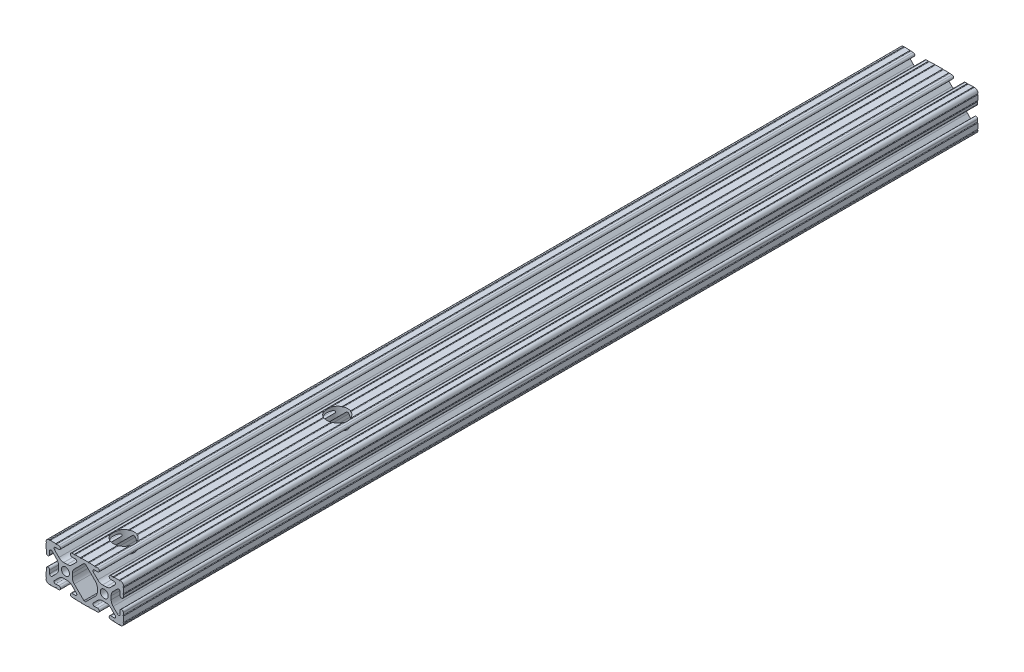
SolidWorks part; units mm, degrees
ref_plane "Front Plane" through (0, 0, 0) normal (0, 0, 1) x (1, 0, 0)
ref_plane "Top Plane" through (0, 0, 0) normal (0, 1, 0) x (1, 0, 0)
ref_plane "Right Plane" through (0, 0, 0) normal (1, 0, 0) x (0, 0, -1)
sketch "Sketch1" plane through (0, 0, 0) normal (0, 0, 1) x (1, 0, 0)
  line L0 (0, 12.7) -> (-12.7814, 12.7) construction
  line L1 (-4.5085, 0) -> (-4.5085, 2.9459)
  line L2 (-6.0437, 12.5461) -> (-10.0976, 12.6876) construction
  line L3 (-11.5616, 12.4229) -> (-4.3159, 12.1699) construction
  line L4 (-6.4364, 10.3486) -> (-6.3592, 12.5571) construction
  line L6 (-2.9459, 4.5085) -> (0, 4.5085)
  line L7 (0, 0) -> (0, 12.7) construction
  line L8 (0, 0) -> (-12.7814, 0) construction
  line L9 (0.7813, 0.7813) -> (-0.7813, -0.7813) construction
  line L10 (-2.9459, 4.5085) -> (-7.1484, 8.711)
  line L11 (-4.5085, 2.9459) -> (-8.711, 7.1484)
  line L13 (0, 0) -> (-12.7814, 12.7814) construction
  line L14 (-10.4131, 12.6987) -> (-4.3048, 12.4853)
  line L15 (-4.3048, 12.4853) -> (-4.382, 10.2769) construction
  line L16 (-4.382, 10.2769) -> (-6.4364, 10.3486)
  line L17 (-12.6987, 10.4131) -> (-12.4853, 4.3048)
  line L18 (-10.2769, 4.382) -> (-10.3486, 6.4364)
  circle A0 centre (0, 0) radius 2.6035
  arc A1 (-4.382, 10.2769) -> (-4.3048, 12.4853) centre (-4.3434, 11.3811) ccw
  arc A2 (-7.1484, 8.711) -> (-6.4364, 10.3486) centre (-6.4698, 9.3896) cw
  arc A3 (-8.711, 7.1484) -> (-10.3486, 6.4364) centre (-9.3896, 6.4698) ccw
  arc A4 (-10.2769, 4.382) -> (-12.4853, 4.3048) centre (-11.3811, 4.3434) cw
  arc A5 (-10.4131, 12.6987) -> (-12.6987, 10.4131) centre (-10.4902, 10.4902) ccw
  arc A6 (-10.4131, 12.6987) -> (-9.7821, 12.6766) centre (-10.0976, 12.6876) ccw
  arc A7 (-6.3592, 12.5571) -> (-5.7282, 12.5351) centre (-6.0437, 12.5461) ccw
  arc A8 (-12.5571, 6.3592) -> (-12.5351, 5.7282) centre (-12.5461, 6.0437) cw
  arc A9 (-12.6987, 10.4131) -> (-12.6766, 9.7821) centre (-12.6876, 10.0976) cw
  dimension "D1" = 5.207
  dimension "D5" = 14.859
  dimension "D9" = 2
  dimension "D2" = 25.4
  dimension "D12" = 0.6314
  dimension "D10" = 2.2098
  dimension "D3" = 9.017
  dimension "D4" = 9.017
  dimension "D6" = 25.4
  dimension "D7" = 6.477
  dimension "D8" = 2.2098
  dimension "D11" = 12.7
sketch "Sketch3" plane through (0, 0, 0) normal (0, 0, 1) x (1, 0, 0)
  line L0 (-2.9459, 4.5085) -> (0, 4.5085) construction
  line L1 (-2.9459, 4.5085) -> (-7.1484, 8.711) construction
  line L2 (-4.382, 10.2769) -> (-6.4364, 10.3486) construction
  line L3 (-10.4131, 12.6987) -> (-4.3048, 12.4853) construction
  line L4 (-4.5085, 0) -> (-4.5085, 2.9459) construction
  line L5 (-4.5085, 2.9459) -> (-8.711, 7.1484) construction
  line L6 (-10.2769, 4.382) -> (-10.3486, 6.4364) construction
  line L7 (-12.6987, 10.4131) -> (-12.4853, 4.3048) construction
  line L8 (-1.1153, 4.5085) -> (1.1153, 4.5085)
  line L9 (-4.2404, 5.803) -> (-7.1484, 8.711)
  line L10 (-4.382, 10.2769) -> (-6.4364, 10.3486)
  line L11 (-9.7821, 12.6766) -> (-6.3592, 12.5571)
  line L12 (-4.5085, -1.1153) -> (-4.5085, 1.1153)
  line L13 (-5.803, 4.2404) -> (-8.711, 7.1484)
  line L14 (-10.2769, 4.382) -> (-10.3486, 6.4364)
  line L15 (-12.6766, 9.7821) -> (-12.5571, 6.3592)
  line L16 (-5.7282, 12.5351) -> (-4.3048, 12.4853)
  line L17 (-12.5351, 5.7282) -> (-12.4853, 4.3048)
  line L18 (0, 0) -> (0, 12.7) construction
  line L19 (0, 0) -> (-12.7814, 0) construction
  line L20 (0, 0) -> (12.7, 0) construction
  line L21 (5.7282, 12.5351) -> (4.3048, 12.4853)
  line L22 (12.7, 10.5674) -> (12.7, 12.6987) construction
  line L23 (10.4131, 12.6987) -> (14.9869, 12.6987)
  line L24 (5.803, 4.2404) -> (12.1093, 10.5467)
  line L25 (4.5085, -1.1153) -> (4.5085, 1.1153)
  line L26 (9.7821, 12.6766) -> (6.3592, 12.5571)
  line L27 (4.382, 10.2769) -> (6.4364, 10.3486)
  line L28 (4.2404, 5.803) -> (7.1484, 8.711)
  line L29 (4.2404, -5.803) -> (7.1484, -8.711)
  line L30 (4.382, -10.2769) -> (6.4364, -10.3486)
  line L31 (9.7821, -12.6766) -> (6.3592, -12.5571)
  line L32 (5.803, -4.2404) -> (12.1093, -10.5467)
  line L33 (12.1093, 10.5467) -> (12.7, 10.5674)
  line L34 (10.4131, -12.6987) -> (14.9869, -12.6987)
  line L35 (5.7282, -12.5351) -> (4.3048, -12.4853)
  line L36 (12.7, -10.5674) -> (12.7, -12.6987) construction
  line L37 (-12.5351, -5.7282) -> (-12.4853, -4.3048)
  line L38 (-5.7282, -12.5351) -> (-4.3048, -12.4853)
  line L39 (-12.6766, -9.7821) -> (-12.5571, -6.3592)
  line L40 (-10.2769, -4.382) -> (-10.3486, -6.4364)
  line L41 (-5.803, -4.2404) -> (-8.711, -7.1484)
  line L42 (-9.7821, -12.6766) -> (-6.3592, -12.5571)
  line L43 (-4.382, -10.2769) -> (-6.4364, -10.3486)
  line L44 (-4.2404, -5.803) -> (-7.1484, -8.711)
  line L45 (-1.1153, -4.5085) -> (1.1153, -4.5085)
  line L46 (12.1093, -10.5467) -> (12.7, -10.5674)
  line L47 (13.2907, -10.5467) -> (12.7, -10.5674)
  line L48 (26.5153, -4.5085) -> (24.2847, -4.5085)
  line L49 (29.6404, -5.803) -> (32.5484, -8.711)
  line L50 (29.782, -10.2769) -> (31.8364, -10.3486)
  line L51 (35.1821, -12.6766) -> (31.7592, -12.5571)
  line L52 (31.203, -4.2404) -> (34.111, -7.1484)
  line L53 (35.6769, -4.382) -> (35.7486, -6.4364)
  line L54 (38.0766, -9.7821) -> (37.9571, -6.3592)
  line L55 (31.1282, -12.5351) -> (29.7048, -12.4853)
  line L56 (37.9351, -5.7282) -> (37.8853, -4.3048)
  line L57 (19.6718, -12.5351) -> (21.0952, -12.4853)
  line L58 (13.2907, 10.5467) -> (12.7, 10.5674)
  line L59 (19.597, -4.2404) -> (13.2907, -10.5467)
  line L60 (15.6179, -12.6766) -> (19.0408, -12.5571)
  line L61 (21.018, -10.2769) -> (18.9636, -10.3486)
  line L62 (21.1596, -5.803) -> (18.2516, -8.711)
  line L63 (21.1596, 5.803) -> (18.2516, 8.711)
  line L64 (21.018, 10.2769) -> (18.9636, 10.3486)
  line L65 (15.6179, 12.6766) -> (19.0408, 12.5571)
  line L66 (20.8915, -1.1153) -> (20.8915, 1.1153)
  line L67 (19.597, 4.2404) -> (13.2907, 10.5467)
  line L68 (19.6718, 12.5351) -> (21.0952, 12.4853)
  line L69 (37.9351, 5.7282) -> (37.8853, 4.3048)
  line L70 (31.1282, 12.5351) -> (29.7048, 12.4853)
  line L71 (38.0766, 9.7821) -> (37.9571, 6.3592)
  line L72 (35.6769, 4.382) -> (35.7486, 6.4364)
  line L73 (31.203, 4.2404) -> (34.111, 7.1484)
  line L74 (29.9085, -1.1153) -> (29.9085, 1.1153)
  line L75 (35.1821, 12.6766) -> (31.7592, 12.5571)
  line L76 (29.782, 10.2769) -> (31.8364, 10.3486)
  line L77 (29.6404, 5.803) -> (32.5484, 8.711)
  line L78 (26.5153, 4.5085) -> (24.2847, 4.5085)
  arc A0 (-10.4131, 12.6987) -> (-9.7821, 12.6766) centre (-10.0976, 12.6876) ccw construction
  arc A1 (-6.4364, 10.3486) -> (-7.1484, 8.711) centre (-6.4698, 9.3896) ccw construction
  arc A2 (-4.382, 10.2769) -> (-4.3048, 12.4853) centre (-4.3434, 11.3811) ccw construction
  arc A3 (-8.711, 7.1484) -> (-10.3486, 6.4364) centre (-9.3896, 6.4698) ccw construction
  arc A4 (-12.4853, 4.3048) -> (-10.2769, 4.382) centre (-11.3811, 4.3434) ccw construction
  arc A5 (-6.3592, 12.5571) -> (-5.7282, 12.5351) centre (-6.0437, 12.5461) ccw construction
  arc A6 (-10.4131, 12.6987) -> (-12.6987, 10.4131) centre (-10.4902, 10.4902) ccw construction
  arc A7 (-12.6766, 9.7821) -> (-12.6987, 10.4131) centre (-12.6876, 10.0976) ccw construction
  arc A8 (-12.5351, 5.7282) -> (-12.5571, 6.3592) centre (-12.5461, 6.0437) ccw construction
  arc A9 (-10.4131, 12.6987) -> (-9.7821, 12.6766) centre (-10.0976, 12.6876) ccw
  arc A10 (-6.4364, 10.3486) -> (-7.1484, 8.711) centre (-6.4698, 9.3896) ccw
  arc A11 (-4.382, 10.2769) -> (-4.3048, 12.4853) centre (-4.3434, 11.3811) ccw
  arc A12 (-8.711, 7.1484) -> (-10.3486, 6.4364) centre (-9.3896, 6.4698) ccw
  arc A13 (-12.4853, 4.3048) -> (-10.2769, 4.382) centre (-11.3811, 4.3434) ccw
  arc A14 (-6.3592, 12.5571) -> (-5.7282, 12.5351) centre (-6.0437, 12.5461) ccw
  arc A15 (-10.4131, 12.6987) -> (-12.6987, 10.4131) centre (-10.4902, 10.4902) ccw
  arc A16 (-12.6766, 9.7821) -> (-12.6987, 10.4131) centre (-12.6876, 10.0976) ccw
  arc A17 (-12.5351, 5.7282) -> (-12.5571, 6.3592) centre (-12.5461, 6.0437) ccw
  arc A18 (-1.1153, 4.5085) -> (-4.2404, 5.803) centre (-1.1153, 8.9281) cw
  arc A19 (4.5085, 1.1153) -> (5.803, 4.2404) centre (8.9281, 1.1153) cw
  arc A20 (1.1153, 4.5085) -> (4.2404, 5.803) centre (1.1153, 8.9281) ccw
  arc A21 (-4.5085, 1.1153) -> (-5.803, 4.2404) centre (-8.9281, 1.1153) ccw
  circle A22 centre (25.4, 0) radius 2.6035
  arc A23 (35.8131, -12.6987) -> (35.1821, -12.6766) centre (35.4976, -12.6876) ccw
  arc A24 (31.8364, -10.3486) -> (32.5484, -8.711) centre (31.8698, -9.3896) ccw
  arc A25 (6.3592, 12.5571) -> (5.7282, 12.5351) centre (6.0437, 12.5461) cw
  arc A26 (29.782, -10.2769) -> (29.7048, -12.4853) centre (29.7434, -11.3811) ccw
  arc A27 (34.111, -7.1484) -> (35.7486, -6.4364) centre (34.7896, -6.4698) ccw
  arc A28 (4.382, 10.2769) -> (4.3048, 12.4853) centre (4.3434, 11.3811) cw
  arc A29 (6.4364, 10.3486) -> (7.1484, 8.711) centre (6.4698, 9.3896) cw
  arc A30 (10.4131, 12.6987) -> (9.7821, 12.6766) centre (10.0976, 12.6876) cw
  arc A31 (10.4131, -12.6987) -> (9.7821, -12.6766) centre (10.0976, -12.6876) ccw
  arc A32 (6.4364, -10.3486) -> (7.1484, -8.711) centre (6.4698, -9.3896) ccw
  arc A33 (4.382, -10.2769) -> (4.3048, -12.4853) centre (4.3434, -11.3811) ccw
  arc A34 (37.8853, -4.3048) -> (35.6769, -4.382) centre (36.7811, -4.3434) ccw
  arc A35 (31.7592, -12.5571) -> (31.1282, -12.5351) centre (31.4437, -12.5461) ccw
  arc A36 (6.3592, -12.5571) -> (5.7282, -12.5351) centre (6.0437, -12.5461) ccw
  arc A37 (35.8131, -12.6987) -> (38.0987, -10.4131) centre (35.8902, -10.4902) ccw
  arc A38 (38.0766, -9.7821) -> (38.0987, -10.4131) centre (38.0876, -10.0976) ccw
  arc A39 (37.9351, -5.7282) -> (37.9571, -6.3592) centre (37.9461, -6.0437) ccw
  arc A40 (-4.5085, -1.1153) -> (-5.803, -4.2404) centre (-8.9281, -1.1153) cw
  arc A41 (1.1153, -4.5085) -> (4.2404, -5.803) centre (1.1153, -8.9281) cw
  arc A42 (4.5085, -1.1153) -> (5.803, -4.2404) centre (8.9281, -1.1153) ccw
  arc A43 (-1.1153, -4.5085) -> (-4.2404, -5.803) centre (-1.1153, -8.9281) ccw
  arc A44 (-12.5351, -5.7282) -> (-12.5571, -6.3592) centre (-12.5461, -6.0437) cw
  arc A45 (-12.6766, -9.7821) -> (-12.6987, -10.4131) centre (-12.6876, -10.0976) cw
  arc A46 (-10.4131, -12.6987) -> (-12.6987, -10.4131) centre (-10.4902, -10.4902) cw
  arc A47 (-6.3592, -12.5571) -> (-5.7282, -12.5351) centre (-6.0437, -12.5461) cw
  arc A48 (-12.4853, -4.3048) -> (-10.2769, -4.382) centre (-11.3811, -4.3434) cw
  arc A49 (-8.711, -7.1484) -> (-10.3486, -6.4364) centre (-9.3896, -6.4698) cw
  arc A50 (-4.382, -10.2769) -> (-4.3048, -12.4853) centre (-4.3434, -11.3811) cw
  arc A51 (-6.4364, -10.3486) -> (-7.1484, -8.711) centre (-6.4698, -9.3896) cw
  arc A52 (-10.4131, -12.6987) -> (-9.7821, -12.6766) centre (-10.0976, -12.6876) cw
  circle A53 centre (0, 0) radius 2.6035 construction
  circle A54 centre (0, 0) radius 2.6035
  arc A55 (26.5153, -4.5085) -> (29.6404, -5.803) centre (26.5153, -8.9281) cw
  arc A56 (20.8915, -1.1153) -> (19.597, -4.2404) centre (16.4719, -1.1153) cw
  arc A57 (24.2847, -4.5085) -> (21.1596, -5.803) centre (24.2847, -8.9281) ccw
  arc A58 (29.9085, -1.1153) -> (31.203, -4.2404) centre (34.3281, -1.1153) ccw
  arc A59 (19.0408, -12.5571) -> (19.6718, -12.5351) centre (19.3563, -12.5461) cw
  arc A60 (21.018, -10.2769) -> (21.0952, -12.4853) centre (21.0566, -11.3811) cw
  arc A61 (18.9636, -10.3486) -> (18.2516, -8.711) centre (18.9302, -9.3896) cw
  arc A62 (14.9869, -12.6987) -> (15.6179, -12.6766) centre (15.3024, -12.6876) cw
  arc A63 (14.9869, 12.6987) -> (15.6179, 12.6766) centre (15.3024, 12.6876) ccw
  arc A64 (18.9636, 10.3486) -> (18.2516, 8.711) centre (18.9302, 9.3896) ccw
  arc A65 (21.018, 10.2769) -> (21.0952, 12.4853) centre (21.0566, 11.3811) ccw
  arc A66 (19.0408, 12.5571) -> (19.6718, 12.5351) centre (19.3563, 12.5461) ccw
  arc A67 (29.9085, 1.1153) -> (31.203, 4.2404) centre (34.3281, 1.1153) cw
  arc A68 (24.2847, 4.5085) -> (21.1596, 5.803) centre (24.2847, 8.9281) cw
  arc A69 (20.8915, 1.1153) -> (19.597, 4.2404) centre (16.4719, 1.1153) ccw
  arc A70 (26.5153, 4.5085) -> (29.6404, 5.803) centre (26.5153, 8.9281) ccw
  arc A71 (37.9351, 5.7282) -> (37.9571, 6.3592) centre (37.9461, 6.0437) cw
  arc A72 (38.0766, 9.7821) -> (38.0987, 10.4131) centre (38.0876, 10.0976) cw
  arc A73 (35.8131, 12.6987) -> (38.0987, 10.4131) centre (35.8902, 10.4902) cw
  arc A74 (31.7592, 12.5571) -> (31.1282, 12.5351) centre (31.4437, 12.5461) cw
  arc A75 (37.8853, 4.3048) -> (35.6769, 4.382) centre (36.7811, 4.3434) cw
  arc A76 (34.111, 7.1484) -> (35.7486, 6.4364) centre (34.7896, 6.4698) cw
  arc A77 (29.782, 10.2769) -> (29.7048, 12.4853) centre (29.7434, 11.3811) cw
  arc A78 (31.8364, 10.3486) -> (32.5484, 8.711) centre (31.8698, 9.3896) cw
  arc A79 (35.8131, 12.6987) -> (35.1821, 12.6766) centre (35.4976, 12.6876) cw
  point P135 (4.5085, 0)
  point P218 (20.8915, 0)
  dimension "D2" = 4.4196
  dimension "D1" = 12.7
extrude "Extrude1" add sketch "Sketch3" along normal mid plane 558.8
sketch "Sketch4" plane through (0, 12.6987, 0) normal (0, 1, 0) x (1, 0, 0)
  line L0 (12.7, -279.4) -> (12.7, -254)
  line L1 (14.9869, -279.4) -> (10.4131, -279.4) construction
  line L2 (12.7, -254) -> (12.7, -114.3)
  circle A0 centre (12.7, -254) radius 6.75
  circle A1 centre (12.7, -114.3) radius 6.75
  line M2 (10.4131, 279.4) -> (10.4131, -279.4)
  line M4 (14.9869, -279.4) -> (14.9869, 279.4)
  dimension "D2" = 13.5
  dimension "D4" = 13.5
  dimension "D1" = 25.4
  dimension "D3" = 139.7
extrude "Cut-Extrude2" cut sketch "Sketch4" against normal through all contours A0 M4 | L0 A0 L2 M4 | A0 L0 L2 M2 | A0 M2 | A1 M4 | A1 M2 M4 | A1 M2 region at (11.568, 12.6987, 254) region at (13.832, 12.6987, 254) region at (8.565, 12.6987, 254) region at (16.835, 12.6987, 254) region at (11.5638, 12.6987, 120.809) region at (8.565, 12.6987, 114.3) region at (16.835, 12.6987, 114.3)
equation "\"D10@Sketch1\" = \"D8@Sketch1\""
equation "\"D11@Sketch1\" = \"D6@Sketch1\"/2"
equation "\"D12@Sketch1\" = \"D8@Sketch1\"/3.5"
equation "\"D2@Sketch3\" = \"D8@Sketch1\"*2"
